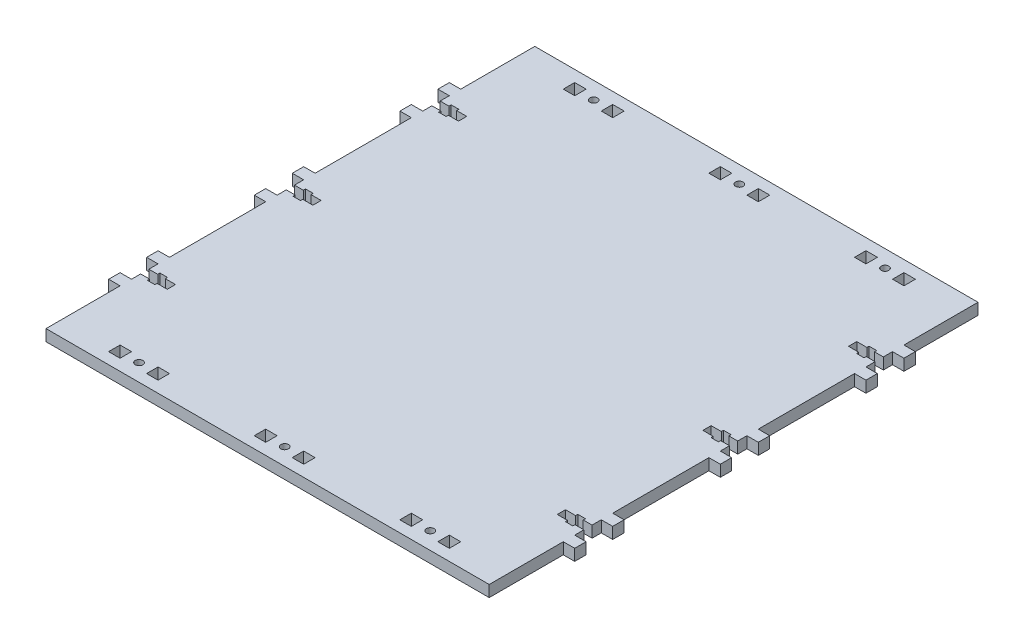
SolidWorks part; units mm, degrees
ref_plane "Front Plane" through (0, 0, 0) normal (0, 0, 1) x (1, 0, 0)
ref_plane "Top Plane" through (0, 0, 0) normal (0, 1, 0) x (1, 0, 0)
ref_plane "Right Plane" through (0, 0, 0) normal (1, 0, 0) x (0, 0, -1)
sketch "Sketch1" plane through (0, 0, 0) normal (0, 1, 0) x (1, 0, 0)
  line L0 (0, 0) -> (0, 159.925) construction
  line L1 (-175, -175) -> (175, -175) construction
  line L2 (-175, -175) -> (-175, 175) construction
  line L3 (-175, 175) -> (175, 175) construction
  line L4 (175, -175) -> (175, 175) construction
  line L5 (-175, -175) -> (175, 175) construction
  line L6 (-175, 175) -> (175, -175) construction
  line L7 (-175, -193) -> (175, -193)
  line L8 (-175, -193) -> (-175, 193)
  line L9 (-175, 193) -> (175, 193)
  line L10 (175, -193) -> (175, 193)
  line L11 (-175, -193) -> (175, 193) construction
  line L12 (-175, 193) -> (175, -193) construction
  line L13 (0, 0) -> (-128.731, 0) construction
  point P0 (0, 0)
  point P6 (0, 0)
  line B0 (0, 179.525) -> (-15, 179.525) construction
  line B1 (0, 184.9951) -> (0, 174.5131) construction
  line B2 (19.525, 184.05) -> (10.475, 184.05)
  line B3 (-19.525, 175) -> (-10.475, 175)
  line B4 (-19.525, 175) -> (-19.525, 184.05)
  line B5 (-19.525, 184.05) -> (-10.475, 184.05)
  line B6 (-10.475, 175) -> (-10.475, 184.05)
  line B7 (-19.525, 175) -> (-10.475, 184.05) construction
  line B8 (-19.525, 184.05) -> (-10.475, 175) construction
  line B9 (10.475, 175) -> (10.475, 184.05)
  line B10 (19.525, 175) -> (10.475, 175)
  line B11 (19.525, 175) -> (19.525, 184.05)
  circle B12 centre (0, 179.525) radius 3
  line B13 (-115, 179.525) -> (-130, 179.525) construction
  line B14 (-115, 184.9951) -> (-115, 174.5131) construction
  line B15 (-95.475, 184.05) -> (-104.525, 184.05)
  line B16 (-134.525, 175) -> (-125.475, 175)
  line B17 (-134.525, 175) -> (-134.525, 184.05)
  line B18 (-134.525, 184.05) -> (-125.475, 184.05)
  line B19 (-125.475, 175) -> (-125.475, 184.05)
  line B20 (-134.525, 175) -> (-125.475, 184.05) construction
  line B21 (-134.525, 184.05) -> (-125.475, 175) construction
  line B22 (-104.525, 175) -> (-104.525, 184.05)
  line B23 (-95.475, 175) -> (-104.525, 175)
  line B24 (-95.475, 175) -> (-95.475, 184.05)
  circle B25 centre (-115, 179.525) radius 3
  line B26 (-175, 19.5) -> (-184, 19.5)
  line B27 (-184, 19.5) -> (-184, 10.5)
  line B28 (-184, 10.5) -> (-175, 10.5)
  line B29 (-175, 10.5) -> (-175, 3.25)
  line B30 (-175, 3.25) -> (-168, 3.25)
  line B31 (-168, 3.25) -> (-168, 4.975)
  line B32 (-168, 4.975) -> (-162, 4.975)
  line B33 (-162, 4.975) -> (-162, 3.25)
  line B34 (-162, 3.25) -> (-154, 3.25)
  line B35 (-154, 3.25) -> (-154, -3.25)
  line B36 (-154, 0) -> (-175, 0) construction
  line B37 (-162, -3.25) -> (-154, -3.25)
  line B38 (-162, -4.975) -> (-162, -3.25)
  line B39 (-168, -4.975) -> (-162, -4.975)
  line B40 (-168, -3.25) -> (-168, -4.975)
  line B41 (-175, -3.25) -> (-168, -3.25)
  line B42 (-175, -10.5) -> (-175, -3.25)
  line B43 (-184, -10.5) -> (-175, -10.5)
  line B44 (-184, -19.5) -> (-184, -10.5)
  line B45 (-175, -19.5) -> (-184, -19.5)
  line B46 (-175, 134.5) -> (-184, 134.5)
  line B47 (-184, 134.5) -> (-184, 125.5)
  line B48 (-184, 125.5) -> (-175, 125.5)
  line B49 (-175, 125.5) -> (-175, 118.25)
  line B50 (-175, 118.25) -> (-168, 118.25)
  line B51 (-168, 118.25) -> (-168, 119.975)
  line B52 (-168, 119.975) -> (-162, 119.975)
  line B53 (-162, 119.975) -> (-162, 118.25)
  line B54 (-162, 118.25) -> (-154, 118.25)
  line B55 (-154, 118.25) -> (-154, 111.75)
  line B56 (-154, 115) -> (-175, 115) construction
  line B57 (-162, 111.75) -> (-154, 111.75)
  line B58 (-162, 110.025) -> (-162, 111.75)
  line B59 (-168, 110.025) -> (-162, 110.025)
  line B60 (-168, 111.75) -> (-168, 110.025)
  line B61 (-175, 111.75) -> (-168, 111.75)
  line B62 (-175, 104.5) -> (-175, 111.75)
  line B63 (-184, 104.5) -> (-175, 104.5)
  line B64 (-184, 95.5) -> (-184, 104.5)
  line B65 (-175, 95.5) -> (-184, 95.5)
  line B66 (115, 179.525) -> (130, 179.525) construction
  line B67 (115, 184.9951) -> (115, 174.5131) construction
  line B68 (95.475, 184.05) -> (104.525, 184.05)
  line B69 (134.525, 175) -> (125.475, 175)
  line B70 (134.525, 175) -> (134.525, 184.05)
  line B71 (134.525, 184.05) -> (125.475, 184.05)
  line B72 (125.475, 175) -> (125.475, 184.05)
  line B73 (134.525, 175) -> (125.475, 184.05) construction
  line B74 (134.525, 184.05) -> (125.475, 175) construction
  line B75 (104.525, 175) -> (104.525, 184.05)
  line B76 (95.475, 175) -> (104.525, 175)
  line B77 (95.475, 175) -> (95.475, 184.05)
  circle B78 centre (115, 179.525) radius 3
  line B79 (175, 19.5) -> (184, 19.5)
  line B80 (184, 19.5) -> (184, 10.5)
  line B81 (184, 10.5) -> (175, 10.5)
  line B82 (175, 10.5) -> (175, 3.25)
  line B83 (175, 3.25) -> (168, 3.25)
  line B84 (168, 3.25) -> (168, 4.975)
  line B85 (168, 4.975) -> (162, 4.975)
  line B86 (162, 4.975) -> (162, 3.25)
  line B87 (162, 3.25) -> (154, 3.25)
  line B88 (154, 3.25) -> (154, -3.25)
  line B89 (154, 0) -> (175, 0) construction
  line B90 (162, -3.25) -> (154, -3.25)
  line B91 (162, -4.975) -> (162, -3.25)
  line B92 (168, -4.975) -> (162, -4.975)
  line B93 (168, -3.25) -> (168, -4.975)
  line B94 (175, -3.25) -> (168, -3.25)
  line B95 (175, -10.5) -> (175, -3.25)
  line B96 (184, -10.5) -> (175, -10.5)
  line B97 (184, -19.5) -> (184, -10.5)
  line B98 (175, -19.5) -> (184, -19.5)
  line B99 (175, 134.5) -> (184, 134.5)
  line B100 (184, 134.5) -> (184, 125.5)
  line B101 (184, 125.5) -> (175, 125.5)
  line B102 (175, 125.5) -> (175, 118.25)
  line B103 (175, 118.25) -> (168, 118.25)
  line B104 (168, 118.25) -> (168, 119.975)
  line B105 (168, 119.975) -> (162, 119.975)
  line B106 (162, 119.975) -> (162, 118.25)
  line B107 (162, 118.25) -> (154, 118.25)
  line B108 (154, 118.25) -> (154, 111.75)
  line B109 (154, 115) -> (175, 115) construction
  line B110 (162, 111.75) -> (154, 111.75)
  line B111 (162, 110.025) -> (162, 111.75)
  line B112 (168, 110.025) -> (162, 110.025)
  line B113 (168, 111.75) -> (168, 110.025)
  line B114 (175, 111.75) -> (168, 111.75)
  line B115 (175, 104.5) -> (175, 111.75)
  line B116 (184, 104.5) -> (175, 104.5)
  line B117 (184, 95.5) -> (184, 104.5)
  line B118 (175, 95.5) -> (184, 95.5)
  line B119 (-115, -179.525) -> (-130, -179.525) construction
  line B120 (-115, -184.9951) -> (-115, -174.5131) construction
  line B121 (-95.475, -184.05) -> (-104.525, -184.05)
  line B122 (-134.525, -175) -> (-125.475, -175)
  line B123 (-134.525, -175) -> (-134.525, -184.05)
  line B124 (-134.525, -184.05) -> (-125.475, -184.05)
  line B125 (-125.475, -175) -> (-125.475, -184.05)
  line B126 (-134.525, -175) -> (-125.475, -184.05) construction
  line B127 (-134.525, -184.05) -> (-125.475, -175) construction
  line B128 (-104.525, -175) -> (-104.525, -184.05)
  line B129 (-95.475, -175) -> (-104.525, -175)
  line B130 (-95.475, -175) -> (-95.475, -184.05)
  circle B131 centre (-115, -179.525) radius 3
  line B132 (0, -179.525) -> (-15, -179.525) construction
  line B133 (0, -184.9951) -> (0, -174.5131) construction
  line B134 (19.525, -184.05) -> (10.475, -184.05)
  line B135 (-19.525, -175) -> (-10.475, -175)
  line B136 (-19.525, -175) -> (-19.525, -184.05)
  line B137 (-19.525, -184.05) -> (-10.475, -184.05)
  line B138 (-10.475, -175) -> (-10.475, -184.05)
  line B139 (-19.525, -175) -> (-10.475, -184.05) construction
  line B140 (-19.525, -184.05) -> (-10.475, -175) construction
  line B141 (10.475, -175) -> (10.475, -184.05)
  line B142 (19.525, -175) -> (10.475, -175)
  line B143 (19.525, -175) -> (19.525, -184.05)
  circle B144 centre (0, -179.525) radius 3
  line B145 (-175, -134.5) -> (-184, -134.5)
  line B146 (-184, -134.5) -> (-184, -125.5)
  line B147 (-184, -125.5) -> (-175, -125.5)
  line B148 (-175, -125.5) -> (-175, -118.25)
  line B149 (-175, -118.25) -> (-168, -118.25)
  line B150 (-168, -118.25) -> (-168, -119.975)
  line B151 (-168, -119.975) -> (-162, -119.975)
  line B152 (-162, -119.975) -> (-162, -118.25)
  line B153 (-162, -118.25) -> (-154, -118.25)
  line B154 (-154, -118.25) -> (-154, -111.75)
  line B155 (-154, -115) -> (-175, -115) construction
  line B156 (-162, -111.75) -> (-154, -111.75)
  line B157 (-162, -110.025) -> (-162, -111.75)
  line B158 (-168, -110.025) -> (-162, -110.025)
  line B159 (-168, -111.75) -> (-168, -110.025)
  line B160 (-175, -111.75) -> (-168, -111.75)
  line B161 (-175, -104.5) -> (-175, -111.75)
  line B162 (-184, -104.5) -> (-175, -104.5)
  line B163 (-184, -95.5) -> (-184, -104.5)
  line B164 (-175, -95.5) -> (-184, -95.5)
  line B165 (175, -134.5) -> (184, -134.5)
  line B166 (184, -134.5) -> (184, -125.5)
  line B167 (184, -125.5) -> (175, -125.5)
  line B168 (175, -125.5) -> (175, -118.25)
  line B169 (175, -118.25) -> (168, -118.25)
  line B170 (168, -118.25) -> (168, -119.975)
  line B171 (168, -119.975) -> (162, -119.975)
  line B172 (162, -119.975) -> (162, -118.25)
  line B173 (162, -118.25) -> (154, -118.25)
  line B174 (154, -118.25) -> (154, -111.75)
  line B175 (154, -115) -> (175, -115) construction
  line B176 (162, -111.75) -> (154, -111.75)
  line B177 (162, -110.025) -> (162, -111.75)
  line B178 (168, -110.025) -> (162, -110.025)
  line B179 (168, -111.75) -> (168, -110.025)
  line B180 (175, -111.75) -> (168, -111.75)
  line B181 (175, -104.5) -> (175, -111.75)
  line B182 (184, -104.5) -> (175, -104.5)
  line B183 (184, -95.5) -> (184, -104.5)
  line B184 (175, -95.5) -> (184, -95.5)
  line B185 (115, -179.525) -> (130, -179.525) construction
  line B186 (115, -184.9951) -> (115, -174.5131) construction
  line B187 (95.475, -184.05) -> (104.525, -184.05)
  line B188 (134.525, -175) -> (125.475, -175)
  line B189 (134.525, -175) -> (134.525, -184.05)
  line B190 (134.525, -184.05) -> (125.475, -184.05)
  line B191 (125.475, -175) -> (125.475, -184.05)
  line B192 (134.525, -175) -> (125.475, -184.05) construction
  line B193 (134.525, -184.05) -> (125.475, -175) construction
  line B194 (104.525, -175) -> (104.525, -184.05)
  line B195 (95.475, -175) -> (104.525, -175)
  line B196 (95.475, -175) -> (95.475, -184.05)
  circle B197 centre (115, -179.525) radius 3
  dimension "D1" = 350
  dimension "D2" = 350
  dimension "D3" = 18
  dimension "D4" = 60
  dimension "D5" = 60
sketch_block_instance "Insert_9mm_M6_bois-1"
sketch_block "Insert_9mm_M6_bois" parameters "D4"=6, "D1"=9.05, "D2"=9.05, "D3"=15
sketch_block_instance "Insert_9mm_M6_bois-2"
sketch_block_instance "Plot_9mm_M6_bois-1"
sketch_block "Plot_9mm_M6_bois" parameters "D1"=9, "D2"=9, "D3"=16, "D4"=30, "D5"=9.95, "D6"=6.5, "D7"=6, "D8"=8
sketch_block_instance "Plot_9mm_M6_bois-4"
sketch_block_instance "Insert_9mm_M6_bois-4"
sketch_block_instance "Plot_9mm_M6_bois-5"
sketch_block_instance "Plot_9mm_M6_bois-6"
sketch_block_instance "Insert_9mm_M6_bois-5"
sketch_block_instance "Insert_9mm_M6_bois-6"
sketch_block_instance "Plot_9mm_M6_bois-7"
sketch_block_instance "Plot_9mm_M6_bois-8"
sketch_block_instance "Insert_9mm_M6_bois-7"
extrude "Boss-Extrude1" add sketch "Sketch1" along normal blind 9 contours L8 B164 B163 B162 | B27 B28 L8 B26 | B45 L8 B43 B44 | B147 B146 B145 L8 | B65 L8 B63 B64 | B47 B48 L8 B46 | B180 L10 B94 B93 B92 B91 B90 B88 B87 B86 B85 B84 B83 B114 B113 B112 B111 B110 B108 B107 B106 B105 B104 B103 L9 L8 B50 B51 B52 B53 B54 B55 B57 B58 B59 B60 B61 | B166 B167 L10 B165 | B184 L10 B182 B183 | L10 B98 B97 B96 | B81 B80 B79 L10 | B101 B100 B99 L10 | L10 B118 B117 B116 region at (0, 0, 0) region at (-179.5, 0, 130) region at (179.5, 0, 130) region at (-179.5, 0, 100) region at (179.5, 0, 100) region at (-179.5, 0, 15) region at (179.5, 0, 15) region at (-179.5, 0, -15) region at (179.5, 0, -15) region at (-179.5, 0, -100) region at (179.5, 0, -100) region at (-179.5, 0, -130) region at (179.5, 0, -130)
